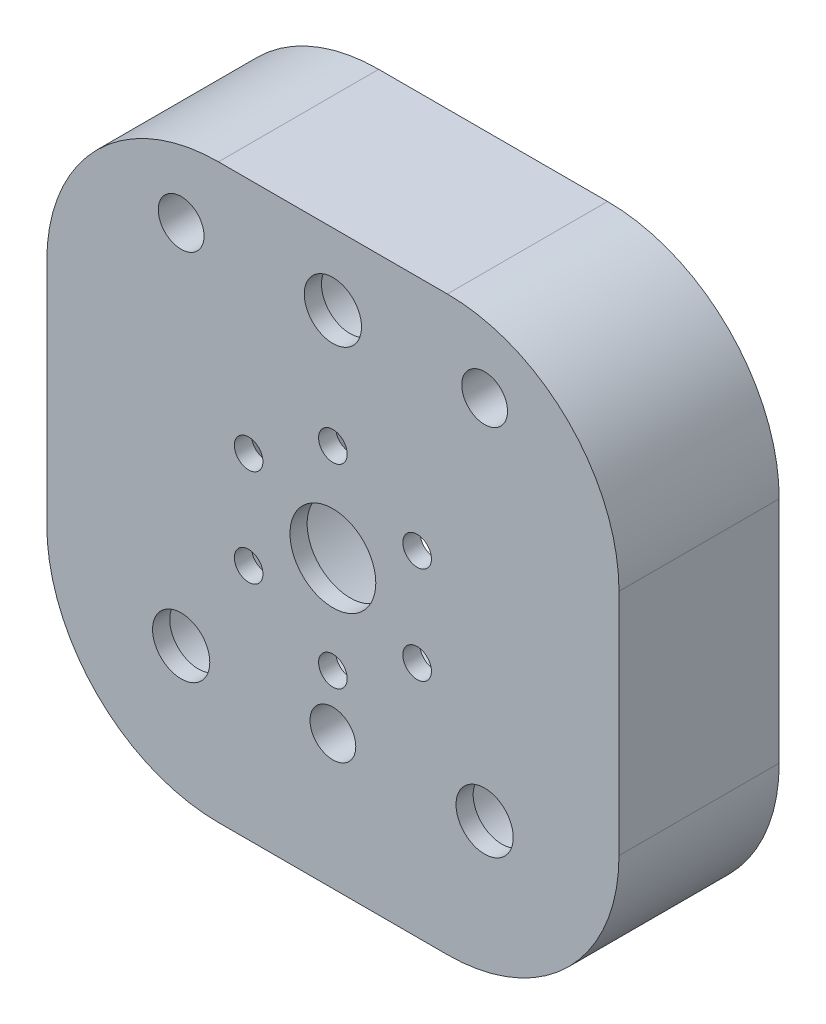
SolidWorks part; units mm, degrees
ref_plane "Front Plane" through (0, 0, 0) normal (0, 0, 1) x (1, 0, 0)
ref_plane "Top Plane" through (0, 0, 0) normal (0, 1, 0) x (1, 0, 0)
ref_plane "Right Plane" through (0, 0, 0) normal (1, 0, 0) x (0, 0, -1)
sketch "Sketch1" plane through (0, 0, 0) normal (0, 0, 1) x (1, 0, 0)
  line L5 (-50, 50) -> (50, 50)
  line L6 (-50, 50) -> (-50, -50)
  line L7 (-50, -50) -> (50, -50)
  line L8 (50, 50) -> (50, -50)
  circle A4 centre (-14.7224, 8.5) radius 2.5 construction
  circle A5 centre (-14.7224, -8.5) radius 2.5 construction
  circle A6 centre (0, -17) radius 2.5 construction
  circle A7 centre (14.7224, -8.5) radius 2.5 construction
  circle A8 centre (14.7224, 8.5) radius 2.5 construction
  circle A9 centre (0, 17) radius 2.5 construction
  circle A10 centre (-14.7224, 8.5) radius 2.5
  circle A11 centre (-14.7224, -8.5) radius 2.5
  circle A12 centre (0, -17) radius 2.5
  circle A13 centre (14.7224, -8.5) radius 2.5
  circle A14 centre (14.7224, 8.5) radius 2.5
  circle A15 centre (0, 17) radius 2.5
  circle A16 centre (0, 0) radius 7.5
  circle A17 centre (0, 37.5) radius 5
  circle A18 centre (-26.5165, -26.5165) radius 5
  circle A19 centre (26.5165, -26.5165) radius 5
  point P5 (0, 50)
  point P17 (-50, 0)
  dimension "D3" = 10
  dimension "D5" = 15
  dimension "D1" = 100
  dimension "D2" = 100
extrude "Boss-Extrude1" add sketch "Sketch1" along normal blind 3
sketch "Sketch2" plane through (0, 0, 0) normal (0, 0, -1) x (-1, 0, 0)
  circle A0 centre (0, 37.5) radius 8.1
  circle A1 centre (26.5165, -26.5165) radius 8.1
  circle A2 centre (-26.5165, -26.5165) radius 8.1
  circle A3 centre (0, 0) radius 22
  line M4 (50, -50) -> (50, 50)
  line M6 (50, 50) -> (-50, 50)
  line M8 (-50, 50) -> (-50, -50)
  line M10 (-50, -50) -> (50, -50)
  dimension "D1" = 16.2
  dimension "D2" = 44
extrude "Boss-Extrude2" add sketch "Sketch2" along normal up to surface (25 mm away) contours A3 A2 A1 A0 M4 M6 M8 M10 region at (0, -48.5858, 0)
fillet "Fillet2" radius 3 3 edges at (-26.5165, -34.6165, -25) (0, 29.4, -25) (26.5165, -34.6165, -25)
fillet "Fillet3" radius 3 1 edges at (0, -22, -25)
sketch "Sketch3" plane through (0, 0, 3) normal (0, 0, 1) x (1, 0, 0)
  circle A0 centre (26.5165, 37.5) radius 4
  circle A1 centre (-26.5165, 37.5) radius 4
  circle A2 centre (0, -26.5165) radius 4
  dimension "D1" = 8
extrude "Cut-Extrude1" cut sketch "Sketch3" against normal offset from surface (25 mm away) 3 up to face at (0, -25, -25)
fillet "Fillet4" radius 30 4 edges at (50, -50, -11) (-50, -50, -11) (-50, 50, -11) (50, 50, -11)
